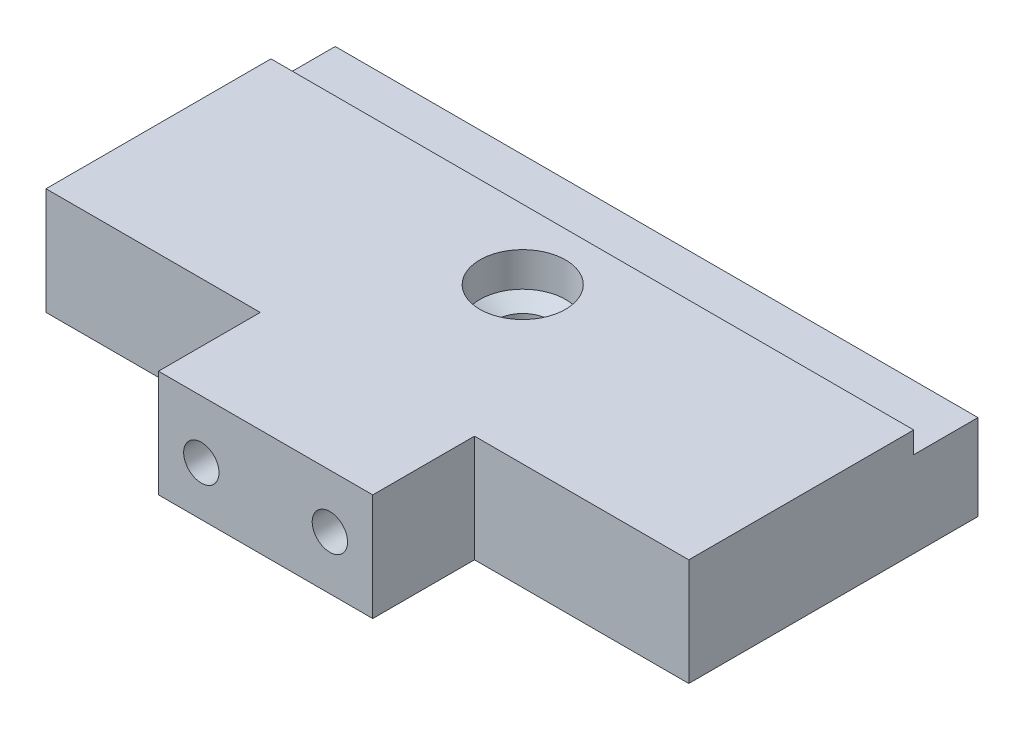
SolidWorks part; units mm, degrees
ref_plane "Front Plane" through (0, 0, 0) normal (0, 0, 1) x (1, 0, 0)
ref_plane "Top Plane" through (0, 0, 0) normal (0, 1, 0) x (1, 0, 0)
ref_plane "Right Plane" through (0, 0, 0) normal (1, 0, 0) x (0, 0, -1)
sketch "Sketch2" plane through (0, 0, 0) normal (0, 1, 0) x (1, 0, 0)
  line L0 (-20, 30.5) -> (-20, 9.5)
  line L1 (0, 0) -> (20, 0)
  line L2 (0, 0) -> (0, 9.5)
  line L3 (0, 9.5) -> (20, 9.5)
  line L4 (20, 0) -> (20, 9.5)
  line L5 (-20, 9.5) -> (40, 9.5)
  line L6 (40, 9.5) -> (40, 30.5)
  line L7 (40, 30.5) -> (-20, 30.5)
  line L10 (-20, 30.5) -> (40, 30.5)
  line L11 (-20, 30.5) -> (-20, 36.5)
  line L12 (-20, 36.5) -> (40, 36.5)
  line L13 (40, 30.5) -> (40, 36.5)
  point P7 (10, 9.5)
  dimension "D1" = 20
  dimension "D2" = 9.5
  dimension "D3" = 60
  dimension "D4" = 21
  dimension "D5" = 6
extrude "Boss-Extrude5" add sketch "Sketch2" along normal blind 10 contours L1 L4 L3 L2 | L6 L7 L0 L5 L3 region at (10, 0, -20) region at (10, 0, -4.75)
extrude "Boss-Extrude6" add sketch "Sketch2<8>" along normal blind 8 contours L7 L13 L12 L11 region at (10, 0, -33.5)
sketch "Sketch2<8>" plane through (0, 0, 0) normal (0, 1, 0) x (1, 0, 0) same geometry as "Sketch2"
sketch "Sketch9" plane through (0, 0, 0) normal (0, 1, 0) x (1, 0, 0)
  line L0 (10, 30.5) -> (10, 0) construction
  line L1 (40, 30.5) -> (-20, 30.5) construction
  line L2 (0, 0) -> (20, 0) construction
  line L3 (6.1619, 24) -> (13.8381, 24) construction
  point P8 (10, 24)
  dimension "D1" = 14.5
hole_wizard "Ø8.0mm Clearance Dowel Hole1" positions "Sketch16" profile "Sketch17" hole size "Ø8.0" standard "DIN"
sketch "Sketch16" plane through (0, 10, 0) normal (0, 1, 0) x (1, 0, 0)
  line L0 (6.1619, 24) -> (13.8381, 24) construction
  point P0 (10, 24)
sketch "Sketch17" plane through (10, 10, -24) normal (1, 0, 0) x (0, 0, 1)
  line L0 (0, 0) -> (0, 5.6034)
  line L1 (0, 5.6034) -> (4, 3.2)
  line L2 (4, 3.2) -> (4, 0)
  line L5 (4, 0) -> (0, 0)
  line L10 (0, 5.6034) -> (-4, 3.2) construction
  line L11 (0, -6.35) -> (0, 107.95) construction
  dimension "Hole Dia." = 8
  dimension "Hole Depth" = 3.2
  dimension "Drill Angle" = 118
hole_wizard "Ø8.0mm Clearance Dowel Hole2" positions "Sketch21" profile "Sketch22" hole size "Ø8.0" standard "DIN"
sketch "Sketch21" plane through (0, 0, 0) normal (0, -1, 0) x (-1, 0, 0)
  point P0 (-10, 24)
sketch "Sketch22" plane through (10, 0, -24) normal (1, 0, 0) x (0, 0, -1)
  line L0 (0, 0) -> (0, 5.4034)
  line L1 (0, 5.4034) -> (4, 3)
  line L2 (4, 3) -> (4, 0)
  line L5 (4, 0) -> (0, 0)
  line L10 (0, 5.4034) -> (-4, 3) construction
  line L11 (0, -6.35) -> (0, 107.95) construction
  dimension "Hole Dia." = 8
  dimension "Hole Depth" = 3
  dimension "Drill Angle" = 118
hole_wizard "Ø5.0mm Clearance Dowel Hole5" positions "Sketch27" profile "Sketch28" hole size "Ø5.0" standard "DIN" end condition through all
sketch "Sketch27" plane through (0, 0, 0) normal (0, -1, 0) x (-1, 0, 0)
  point P0 (-10, 24)
sketch "Sketch28" plane through (10, 0, -24) normal (1, 0, 0) x (0, 0, -1)
  line L0 (0, 0) -> (0, 10)
  line L1 (0, 10) -> (2.5, 10)
  line L2 (2.5, 10) -> (2.5, 0)
  line L5 (2.5, 0) -> (0, 0)
  line L11 (0, -6.35) -> (0, 107.95) construction
  dimension "Thru Hole Dia." = 5
  dimension "Thru Hole Depth" = 10
sketch3d "3DSketch8"
  line L0 (0, 5, 0) -> (20, 5, 0) construction
  line L1 (0, 10, 0) -> (0, 0, 0) construction
  line L2 (20, 10, 0) -> (20, 0, 0) construction
  line L3 (4, 7.2133, 0) -> (4, 1.9966, 0) construction
  line L4 (16, 7.7583, 0) -> (16, 2.2556, 0) construction
  dimension "D1" = 4
  dimension "D2" = 12
  dimension "D3" = 4
hole_wizard "M4 Tapped Hole1" positions "Sketch30" profile "Sketch31" tap size "M4" standard "DIN"
sketch "Sketch30" plane through (0, 0, 0) normal (0, 0, 1) x (1, 0, 0)
  line L0 (4, 7.2133) -> (4, 1.9966) construction
  point P0 (4, 4.605)
sketch "Sketch31" plane through (4, 4.605, 0) normal (1, 0, 0) x (0, -1, 0)
  line L0 (0, 0) -> (0, 11.0914)
  line L1 (0, 11.0914) -> (1.65, 10.1)
  line L2 (1.65, 10.1) -> (1.65, 0)
  line L5 (1.65, 0) -> (0, 0)
  line L10 (0, 11.0914) -> (-1.65, 10.1) construction
  line L11 (0, -6.35) -> (0, 107.95) construction
  dimension "Tap Drill Dia." = 3.3
  dimension "Tap Drill Depth" = 10.1
  dimension "Drill Angle" = 118
cosmetic thread "Hole Thread1" parameters "D1"=8, "D2"=4
hole_wizard "M4 Tapped Hole2" positions "Sketch33" profile "Sketch32" tap size "M4" standard "DIN"
sketch "Sketch33" plane through (0, 0, 0) normal (0, 0, 1) x (1, 0, 0)
  line L0 (16, 7.7583) -> (16, 2.2556) construction
  point P0 (16, 5.0069)
sketch "Sketch32" plane through (16, 5.0069, 0) normal (1, 0, 0) x (0, -1, 0)
  line L0 (0, 0) -> (0, 11.0914)
  line L1 (0, 11.0914) -> (1.65, 10.1)
  line L2 (1.65, 10.1) -> (1.65, 0)
  line L5 (1.65, 0) -> (0, 0)
  line L10 (0, 11.0914) -> (-1.65, 10.1) construction
  line L11 (0, -6.35) -> (0, 107.95) construction
  dimension "Tap Drill Dia." = 3.3
  dimension "Tap Drill Depth" = 10.1
  dimension "Drill Angle" = 118
cosmetic thread "Hole Thread2" parameters "D1"=8, "D2"=4
